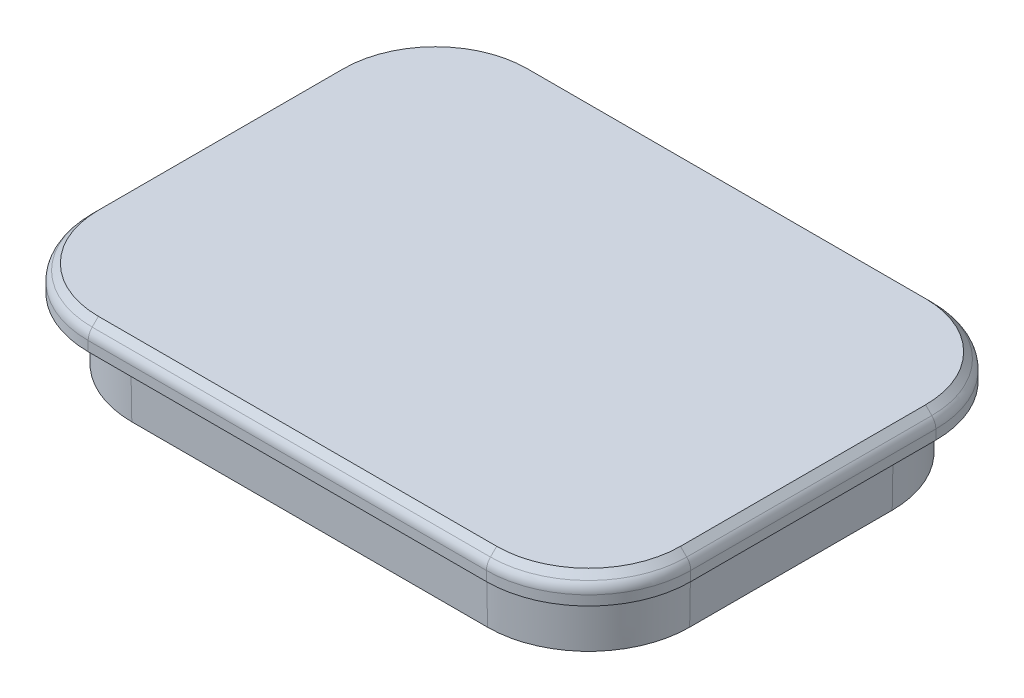
SolidWorks part; units mm, degrees
ref_plane "Front" through (0, 0, 0) normal (0, 0, 1) x (1, 0, 0)
ref_plane "Top" through (0, 0, 0) normal (0, 1, 0) x (1, 0, 0)
ref_plane "Right" through (0, 0, 0) normal (1, 0, 0) x (0, 0, -1)
sketch "Sketch1" plane through (0, 0, 0) normal (0, 1, 0) x (1, 0, 0)
  line L1 (6, 0) -> (26.9, 0)
  line L2 (0, 6) -> (0, 17.9)
  line L3 (6, 23.9) -> (26.9, 23.9)
  line L4 (32.9, 6) -> (32.9, 17.9)
  arc A0 (6, 0) -> (0, 6) centre (6, 6) cw
  arc A1 (26.9, 0) -> (32.9, 6) centre (26.9, 6) ccw
  arc A2 (26.9, 23.9) -> (32.9, 17.9) centre (26.9, 17.9) cw
  arc A3 (0, 17.9) -> (6, 23.9) centre (6, 17.9) cw
  point P7 (0, 0)
  point P10 (32.9, 0)
  point P13 (32.9, 23.9)
  point P16 (0, 23.9)
  dimension "D3" = 6
  dimension "D1" = 32.9
  dimension "D2" = 23.9
extrude "Boss-Extrude1" add sketch "Sketch1" along normal blind 3.6
sketch "Sketch2" plane through (0, 3.6, 0) normal (0, 1, 0) x (1, 0, 0)
  line L0 (0, 17.9) -> (0, 6) construction
  line L1 (4.75, 25.15) -> (28.15, 25.15)
  line L2 (-1.25, 19.15) -> (-1.25, 4.75)
  line L3 (4.75, -1.25) -> (28.15, -1.25)
  line L4 (34.15, 19.15) -> (34.15, 4.75)
  line L5 (26.9, 23.9) -> (6, 23.9) construction
  line L6 (32.9, 6) -> (32.9, 17.9) construction
  line L7 (6, 0) -> (26.9, 0) construction
  arc A0 (-1.25, 4.75) -> (4.75, -1.25) centre (4.75, 4.75) ccw
  arc A1 (28.15, -1.25) -> (34.15, 4.75) centre (28.15, 4.75) ccw
  arc A2 (28.15, 25.15) -> (34.15, 19.15) centre (28.15, 19.15) cw
  arc A3 (4.75, 25.15) -> (-1.25, 19.15) centre (4.75, 19.15) ccw
  dimension "D5" = 6
  dimension "D1" = 1.25
  dimension "D2" = 1.25
  dimension "D3" = 1.25
  dimension "D4" = 1.25
extrude "Boss-Extrude2" add sketch "Sketch2" along normal blind 1.5
sketch "Sketch3" plane through (0, 0, 0) normal (0, -1, 0) x (1, 0, 0)
  line L0 (26.9, -23.9) -> (6, -23.9) construction
  line L1 (25.7, -22.7) -> (7.2, -22.7)
  line L2 (31.7, -16.7) -> (31.7, -7.2)
  line L3 (25.7, -1.2) -> (7.2, -1.2)
  line L4 (1.2, -16.7) -> (1.2, -7.2)
  line L5 (32.9, -6) -> (32.9, -17.9) construction
  line L6 (6, 0) -> (26.9, 0) construction
  line L7 (0, -17.9) -> (0, -6) construction
  arc A0 (7.2, -22.7) -> (1.2, -16.7) centre (7.2, -16.7) cw
  arc A1 (7.2, -1.2) -> (1.2, -7.2) centre (7.2, -7.2) ccw
  arc A2 (31.7, -7.2) -> (25.7, -1.2) centre (25.7, -7.2) ccw
  arc A3 (25.7, -22.7) -> (31.7, -16.7) centre (25.7, -16.7) ccw
  dimension "D5" = 6
  dimension "D1" = 1.2
  dimension "D2" = 1.2
  dimension "D3" = 1.2
  dimension "D4" = 1.2
extrude "Cut-Extrude1" cut sketch "Sketch3" against normal blind 3.6
sketch "Sketch5" plane through (0, 3.6, 0) normal (0, -1, 0) x (1, 0, 0)
  line L0 (7.2, -22.7) -> (25.7, -22.7) construction
  line L1 (7.2, -1.2) -> (8.4, -1.2)
  line L2 (7.2, -1.2) -> (7.2, -6.2)
  line L3 (7.2, -22.7) -> (8.4, -22.7)
  line L4 (8.4, -1.2) -> (8.4, -6.2)
  line L5 (1.2, -7.2) -> (1.2, -16.7) construction
  line L6 (25.7, -1.2) -> (24.5, -1.2)
  line L7 (25.7, -1.2) -> (25.7, -6.2)
  line L8 (25.7, -22.7) -> (24.5, -22.7)
  line L9 (24.5, -1.2) -> (24.5, -6.2)
  line L10 (31.7, -16.7) -> (26.7, -16.7)
  line L11 (31.7, -16.7) -> (31.7, -15.5)
  line L12 (31.7, -15.5) -> (26.7, -15.5)
  line L13 (1.2, -16.7) -> (1.2, -15.5)
  line L14 (31.7, -16.7) -> (31.7, -7.2) construction
  line L15 (1.2, -7.2) -> (6.2, -7.2)
  line L16 (1.2, -7.2) -> (1.2, -8.4)
  line L17 (1.2, -8.4) -> (6.2, -8.4)
  line L18 (31.7, -7.2) -> (31.7, -8.4)
  line L19 (9.4, -7.2) -> (23.5, -7.2)
  line L20 (7.2, -9.4) -> (7.2, -14.5)
  line L21 (9.4, -8.4) -> (23.5, -8.4)
  line L22 (8.4, -9.4) -> (8.4, -14.5)
  line L23 (24.5, -9.4) -> (24.5, -14.5)
  line L24 (25.7, -9.4) -> (25.7, -14.5)
  line L25 (26.7, -7.2) -> (31.7, -7.2)
  line L26 (26.7, -8.4) -> (31.7, -8.4)
  line L27 (23.5, -15.5) -> (9.4, -15.5)
  line L28 (23.5, -16.7) -> (9.4, -16.7)
  line L29 (24.5, -17.7) -> (24.5, -22.7)
  line L30 (25.7, -17.7) -> (25.7, -22.7)
  line L31 (7.2, -17.7) -> (7.2, -22.7)
  line L32 (6.2, -15.5) -> (1.2, -15.5)
  line L33 (8.4, -17.7) -> (8.4, -22.7)
  line L34 (6.2, -16.7) -> (1.2, -16.7)
  arc A0 (23.5, -16.7) -> (24.5, -17.7) centre (23.5, -17.7) cw
  arc A1 (26.7, -16.7) -> (25.7, -17.7) centre (26.7, -17.7) ccw
  arc A2 (26.7, -15.5) -> (25.7, -14.5) centre (26.7, -14.5) cw
  arc A3 (23.5, -15.5) -> (24.5, -14.5) centre (23.5, -14.5) ccw
  arc A4 (25.7, -6.2) -> (26.7, -7.2) centre (26.7, -6.2) ccw
  arc A5 (25.7, -9.4) -> (26.7, -8.4) centre (26.7, -9.4) cw
  arc A6 (24.5, -9.4) -> (23.5, -8.4) centre (23.5, -9.4) ccw
  arc A7 (24.5, -6.2) -> (23.5, -7.2) centre (23.5, -6.2) cw
  arc A8 (9.4, -15.5) -> (8.4, -14.5) centre (9.4, -14.5) cw
  arc A9 (8.4, -17.7) -> (9.4, -16.7) centre (9.4, -17.7) cw
  arc A10 (7.2, -17.7) -> (6.2, -16.7) centre (6.2, -17.7) ccw
  arc A11 (7.2, -14.5) -> (6.2, -15.5) centre (6.2, -14.5) cw
  arc A12 (7.2, -9.4) -> (6.2, -8.4) centre (6.2, -9.4) ccw
  arc A13 (9.4, -8.4) -> (8.4, -9.4) centre (9.4, -9.4) ccw
  arc A14 (9.4, -7.2) -> (8.4, -6.2) centre (9.4, -6.2) cw
  arc A15 (6.2, -7.2) -> (7.2, -6.2) centre (6.2, -6.2) ccw
  point P44 (24.5, -16.7)
  point P47 (25.7, -16.7)
  point P54 (25.7, -7.2)
  point P57 (25.7, -8.4)
  point P68 (7.2, -16.7)
  point P71 (7.2, -15.5)
  point P76 (8.4, -8.4)
  dimension "D5" = 1
  dimension "D1" = 1.2
  dimension "D2" = 1.2
  dimension "D3" = 1.2
  dimension "D4" = 1.2
extrude "Boss-Extrude5" add sketch "Sketch5" along normal blind 3.6
chamfer "Chamfer1" distance 3.6 angle 1 8 edges at (0, 0, -11.95) (1.7574, 0, -1.7574) (1.7574, 0, -22.1426) (16.45, 0, 0) (16.45, 0, -23.9) (31.1426, 0, -1.7574) (31.1426, 0, -22.1426) (32.9, 0, -11.95) first distance on face at (0, 1.8, -11.95) first distance on face at (2.3787, 1.8, -2.3787) first distance on face at (2.3787, 1.8, -21.5213) first distance on face at (16.45, 1.8, 0) first distance on face at (16.45, 1.8, -23.9) first distance on face at (30.5213, 1.8, -2.3787) first distance on face at (30.5213, 1.8, -21.5213) first distance on face at (32.9, 1.8, -11.95)
fillet "Fillet3" radius 1 16 edges at (1.2, 1.8, -16.7) (1.2, 1.8, -8.4) (31.7, 1.8, -8.4) (24.5, 1.8, -1.2) (24.5, 1.8, -22.7) (25.7, 1.8, -1.2) (8.4, 1.8, -1.2) (7.2, 1.8, -1.2) (31.7, 1.8, -16.7) (31.7, 1.8, -7.2) (31.7, 1.8, -15.5) (7.2, 1.8, -22.7) (1.2, 1.8, -7.2) (1.2, 1.8, -15.5) (8.4, 1.8, -22.7) (25.7, 1.8, -22.7)
chamfer "Chamfer2" distance 0.6 angle 45 8 edges at (16.45, 5.1, -25.15) (0.5074, 5.1, -23.3926) (32.3926, 5.1, -23.3926) (-1.25, 5.1, -11.95) (34.15, 5.1, -11.95) (0.5074, 5.1, -0.5074) (32.3926, 5.1, -0.5074) (16.45, 5.1, 1.25)
fillet "Fillet4" radius 0.8 8 edges at (32.3926, 4.5, -0.5074) (34.15, 4.5, -11.95) (32.3926, 4.5, -23.3926) (16.45, 4.5, -25.15) (0.5074, 4.5, -23.3926) (-1.25, 4.5, -11.95) (0.5074, 4.5, -0.5074) (16.45, 4.5, 1.25)
